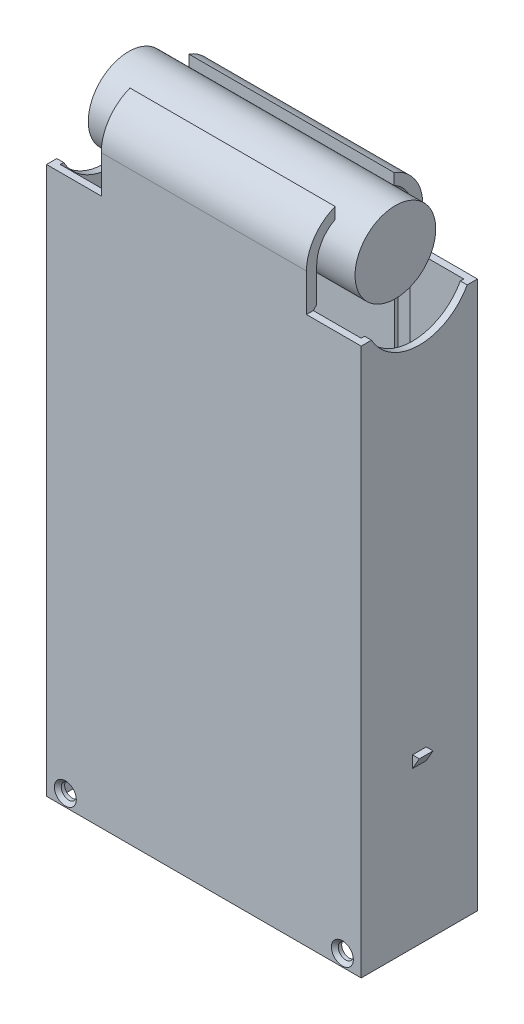
SolidWorks part; units mm, degrees
other "标注1"
sketch "草图12" plane through (-30, 73.1996, 9) normal (-0.0079, 0.9889, 0.1482) x (0.9983, -0.0007, 0.0577)
ref_plane "前视基准面" through (0, 0, 0) normal (0, 0, 1) x (1, 0, 0)
ref_plane "上视基准面" through (0, 0, 0) normal (0, 1, 0) x (1, 0, 0)
ref_plane "右视基准面" through (0, 0, 0) normal (1, 0, 0) x (0, 0, -1)
sketch "草图1" plane through (0, 0, 0) normal (0, 1, 0) x (1, 0, 0)
  line L0 (-22, 7.5) -> (22, 7.5)
  line L1 (-23, -8.5) -> (23, -8.5)
  line L2 (-23, -8.5) -> (-23, 8.5)
  line L3 (-23, 8.5) -> (23, 8.5)
  line L4 (23, -8.5) -> (23, 8.5)
  line L5 (-23, -8.5) -> (23, 8.5) construction
  line L6 (-23, 8.5) -> (23, -8.5) construction
  line L7 (22, -7.5) -> (22, 7.5)
  line L8 (-22, -7.5) -> (22, -7.5)
  line L9 (-22, -7.5) -> (-22, 7.5)
  point P0 (0, 0)
  dimension "D1" = 17
  dimension "D2" = 46
  dimension "D3" = 1
extrude "凸台-拉伸1" add sketch "草图1" along normal blind 80
sketch "草图4" plane through (-23, 0, 0) normal (-1, 0, 0) x (0, 0, 1)
  line L0 (-8.5, 80) -> (8.5, 80) construction
  line L1 (-5.5, 52.5) -> (5.5, 52.5)
  line L2 (-5.5, 52.5) -> (-5.5, 60)
  line L3 (-5.5, 60) -> (5.5, 60)
  line L4 (5.5, 52.5) -> (5.5, 60)
  line L5 (-5.5, 52.5) -> (5.5, 60) construction
  line L6 (-5.5, 60) -> (5.5, 52.5) construction
  line L7 (0, -55) -> (0, 55) construction
  point P0 (0, 56.25)
  dimension "D1" = 20
  dimension "D2" = 7.5
  dimension "D3" = 11
extrude "切除-拉伸1" cut sketch "草图4" against normal blind 30
sketch "草图6" plane through (0, 0, 0) normal (1, 0, 0) x (0, 0, -1)
  line L0 (-8.5, 80) -> (8.5, 80) construction
  circle A0 centre (0, 85.9) radius 5.9
  dimension "D1" = 11.8
extrude "凸台-拉伸4" add sketch "草图6" along normal mid plane 39 separate body
sketch "草图3" plane through (0, 0, 0) normal (1, 0, 0) x (0, 0, -1)
  line L0 (-8.5, 80) -> (-8.5, 85.5)
  line L1 (-7, 85.5) -> (-7, 80)
  line L2 (-8.5, 80) -> (8.5, 80) construction
  line L3 (-7, 80) -> (-8.5, 80)
  line L4 (-4.3004, 91.5793) -> (-4.3004, 89.9394)
  line L5 (0, 25.3) -> (0, -25.3) construction
  line L6 (4.3004, 91.5793) -> (4.3004, 89.9394)
  line L7 (7, 80) -> (8.5, 80)
  line L8 (8.5, 80) -> (8.5, 85.5)
  line L9 (7, 85.5) -> (7, 80)
  line L10 (-8.5, 80) -> (-8.5, 0) construction
  arc A0 (-8.5, 85.5) -> (-4.3004, 91.5793) centre (-2, 85.5) cw
  arc A1 (-7, 85.5) -> (-4.3004, 89.9394) centre (-2, 85.5) cw
  arc A2 (7, 85.5) -> (4.3004, 89.9394) centre (2, 85.5) ccw
  arc A3 (8.5, 85.5) -> (4.3004, 91.5793) centre (2, 85.5) ccw
  circle A4 centre (0, 85.9) radius 5.9 construction
  dimension "D1" = 1.5
  dimension "D2" = 5.5
  dimension "D3" = 5
extrude "凸台-拉伸3" add sketch "草图3" along normal mid plane 30
sketch "草图8" plane through (23, 0, 0) normal (1, 0, 0) x (0, 0, -1)
  line L0 (-8.5, 80) -> (8.5, 80) construction
  line L1 (-7, 80) -> (7, 80)
  line L2 (-7, 80) -> (-7, 85.5) construction
  line L3 (7, 85.5) -> (7, 80) construction
  arc A0 (-7, 80) -> (7, 80) centre (0, 83.873) ccw
  dimension "D1" = 8
extrude "切除-拉伸2" cut sketch "草图8" against normal blind 60
sketch "草图11" plane through (0, 0, -7.5) normal (0, 0, 1) x (1, 0, 0)
  line L0 (-23, 0) -> (23, 0) construction
  line L1 (-14.1, 77) -> (-11.9, 77) construction
  line L2 (-14.1, 77) -> (-14.1, 0)
  line L3 (-14.1, 0) -> (-11.9, 0)
  line L4 (-11.9, 77) -> (-11.9, 0)
  line L5 (-23, 80) -> (-15, 80) construction
  line L6 (0, -9.35) -> (0, 9.35) construction
  line L7 (11.9, 77) -> (11.9, 0)
  line L8 (14.1, 0) -> (11.9, 0)
  line L9 (14.1, 77) -> (14.1, 0)
  line L11 (-14.1, 77) -> (-13, 77.2947)
  line L12 (-13, 77.2947) -> (-11.9, 77)
  line L13 (13, 77.2947) -> (11.9, 77)
  line L14 (14.1, 77) -> (13, 77.2947)
  dimension "D1" = 2.2
  dimension "D2" = 11.9
  dimension "D3" = 3
  dimension "D4" = 15
extrude "切除-拉伸3" cut sketch "草图11" against normal blind 0.5
mirror "镜向1" about plane through (0, 0, 0) normal (0, 0, 1) of "切除-拉伸3"
chamfer "倒角1" distance 1 angle 45 4 edges at (-23, 56.25, 5.5) (-23, 60, 0) (-23, 56.25, -5.5) (-23, 52.5, 0)
sketch "草图13" plane through (0, 0, 8.5) normal (0, 0, 1) x (1, 0, 0)
  line L0 (-23, 22.7679) -> (-24, 24.5)
  line L1 (-23, 80) -> (-23, 0) construction
  line L2 (-24, 24.5) -> (-23, 24.5)
  line L3 (-23, 24.5) -> (-23, 22.7679)
  line L4 (0, -9.35) -> (0, 9.35) construction
  line L5 (23, 24.5) -> (23, 22.7679)
  line L6 (24, 24.5) -> (23, 24.5)
  line L7 (23, 22.7679) -> (24, 24.5)
  line L10 (-23, 80) -> (-15, 80) construction
  dimension "D1" = 30
  dimension "D2" = 1
  dimension "D3" = 55.5
extrude "凸台-拉伸7" add sketch "草图13" against normal blind 2 from offset 7.5 offset against normal yes
chamfer "倒角2" distance 0.5 angle 45 2 edges at (0, 80, 7) (0, 80, -7)
sketch "草图15" plane through (0, 0, 8.5) normal (0, 0, 1) x (1, 0, 0)
  line L10 (-23, 80) -> (-23, 0) construction
  line L11 (-23, 0) -> (23, 0) construction
  line L12 (0, -9.35) -> (0, 9.35) construction
  circle A6 centre (-20.25, 1.75) radius 1.1
  circle A7 centre (20.25, 1.75) radius 1.1
  dimension "D4" = 2.2
  dimension "D1" = 2.75
  dimension "D2" = 1.75
extrude "切除-拉伸5" cut sketch "草图15" against normal blind 40
chamfer "倒角3" distance 0.5 angle 45 4 edges at (21.35, 1.75, -8.5) (-19.15, 1.75, -8.5) (19.15, 1.75, 8.5) (-19.15, 1.75, 8.5)
